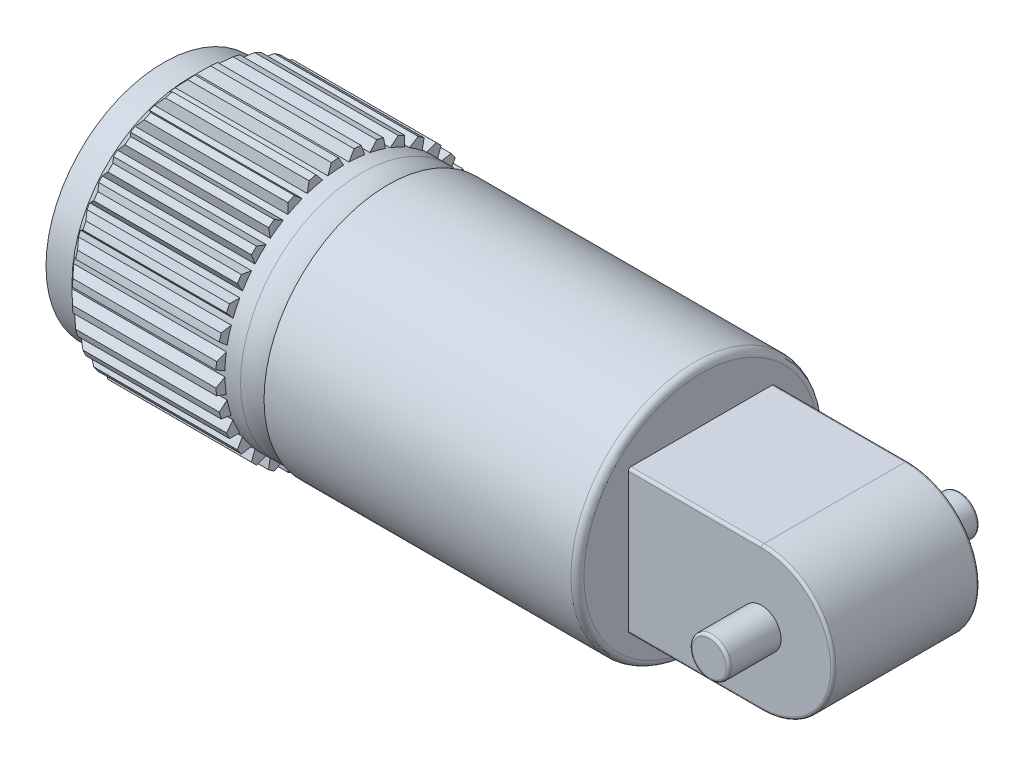
SolidWorks part; units mm, degrees
ref_plane "Спереди" through (0, 0, 0) normal (0, 0, 1) x (1, 0, 0)
ref_plane "Сверху" through (0, 0, 0) normal (0, 1, 0) x (1, 0, 0)
ref_plane "Справа" through (0, 0, 0) normal (1, 0, 0) x (0, 0, -1)
sketch "Эскиз1" plane through (0, 0, 0) normal (0, 0, 1) x (1, 0, 0)
  line L0 (1, 0) -> (20.6, 0)
  line L1 (0, 3.3) -> (0, 4.5)
  line L2 (0, 4.5) -> (1, 4.5)
  line L3 (1, 4.5) -> (1.5, 5)
  line L4 (1.5, 5) -> (7, 5)
  line L5 (7, 5) -> (7, 4.65)
  line L6 (7, 4.65) -> (7.6, 4.65)
  line L7 (8.6, 4.299) -> (8.6, 4.75)
  line L8 (8.6, 4.75) -> (20.6, 4.75)
  line L9 (20.6, 4.75) -> (20.6, 0)
  line L11 (0, 3.3) -> (1, 3.3)
  line L12 (1, 3.3) -> (1, 2.62)
  line L13 (1, 2.62) -> (5, 2.62)
  line L14 (5, 2.62) -> (5, 2.35)
  line L15 (5, 2.35) -> (3, 2.35)
  line L16 (3, 2.35) -> (3, 2.25)
  line L17 (3.05, 0.45) -> (1.45, 0.45)
  line L18 (3, 2.25) -> (3.05, 2.25)
  line L19 (3.05, 2.25) -> (3.05, 0.45)
  arc A0 (7.6, 4.65) -> (8.6, 4.299) centre (7.6, 3.05) cw
  arc A1 (1.45, 0.45) -> (1, 0) centre (1.45, 0) ccw
  dimension "D11" = 1.6
  dimension "D1" = 12
  dimension "D2" = 4.75
  dimension "D3" = 8.6
  dimension "D4" = 4.5
  dimension "D5" = 1
  dimension "D6" = 45
  dimension "D7" = 5
  dimension "D8" = 6
  dimension "D9" = 4.65
  dimension "D10" = 0.6
  dimension "D12" = 3.3
  dimension "D13" = 3
  dimension "D14" = 2.35
  dimension "D15" = 2.62
  dimension "D16" = 1
  dimension "D17" = 5
  dimension "D18" = 0.45
  dimension "D19" = 1
  dimension "D20" = 0.1
  dimension "D21" = 0.05
revolve "Повернуть1" add sketch "Эскиз1" angle 360 about L0
cosmetic thread "Условное изображение резьбы1" parameters "D2"=6
fillet "Скругление1" radius 0.25 1 edges at (20.6, 0, 4.75)
sketch "Эскиз2" plane through (0, 0, 0) normal (0, 0, 1) x (1, 0, 0)
  line L0 (0, 0) -> (20.6, 0) construction
  line L1 (0, 4.5) -> (0, -4.5) construction
  line L2 (20.6, -4.5) -> (20.6, 4.5) construction
  line L4 (20.6, -2.75) -> (25.7, -2.75)
  line L5 (20.6, -2.75) -> (20.6, 2.75)
  line L6 (20.6, 2.75) -> (25.7, 2.75)
  arc A0 (25.7, -2.75) -> (25.7, 2.75) centre (25.7, 0) ccw
  point P13 (28.6, -2.75)
  dimension "D3" = 5.1
  dimension "D1" = 5.5
  dimension "D2" = 8
extrude "Бобышка-Вытянуть1" add sketch "Эскиз2" along normal mid plane 5.6
fillet "Скругление2" radius 0.1 6 edges at (23.15, -2.75, -2.8) (28.45, 0, -2.8) (23.15, -2.75, 2.8) (28.45, 0, 2.8) (23.15, 2.75, -2.8) (23.15, 2.75, 2.8)
sketch "Эскиз3" plane through (0, 0, 2.8) normal (0, 0, 1) x (1, 0, 0)
  line L0 (20.6, 0) -> (25.7, 0) construction
  line L1 (20.6, 2.65) -> (20.6, -2.65) construction
  circle A0 centre (25.7, 0) radius 0.75
  dimension "D1" = 1.5
  dimension "D2" = 5.1
extrude "Бобышка-Вытянуть2" add sketch "Эскиз3" along normal blind 2
fillet "Скругление3" radius 0.1 1 edges at (26.45, 0, 4.8)
mirror "Зеркальное отражение1" about plane through (0, 0, 0) normal (0, 0, 1) of "Скругление3", "Бобышка-Вытянуть2"
sketch "Эскиз4" plane through (7, 0, 0) normal (1, 0, 0) x (0, 0, -1)
  line L0 (0, 0) -> (0, 5) construction
  line L1 (-0.3, 4.991) -> (0, 0) construction
  line L2 (0, 0) -> (0.3, 4.991) construction
  line L3 (-0.3, 4.991) -> (-0.1025, 4.6489)
  line L4 (0.3, 4.991) -> (0.1025, 4.6489)
  circle A0 centre (0, 0) radius 5 construction
  arc A1 (-0.3, 4.991) -> (0.3, 4.991) centre (0, 0) cw
  arc A2 (-0.1025, 4.6489) -> (0.1025, 4.6489) centre (0, 0) cw
  circle A3 centre (0, 0) radius 4.65 construction
  dimension "D1" = 60
  dimension "D2" = 0.6
extrude "Вырез-Вытянуть1" cut sketch "Эскиз4" against normal through all
pattern_circular "Круговой массив1" count 36 over 360 about axis through (1, 0, 0) along (-1, 0, 0) of "Вырез-Вытянуть1"
